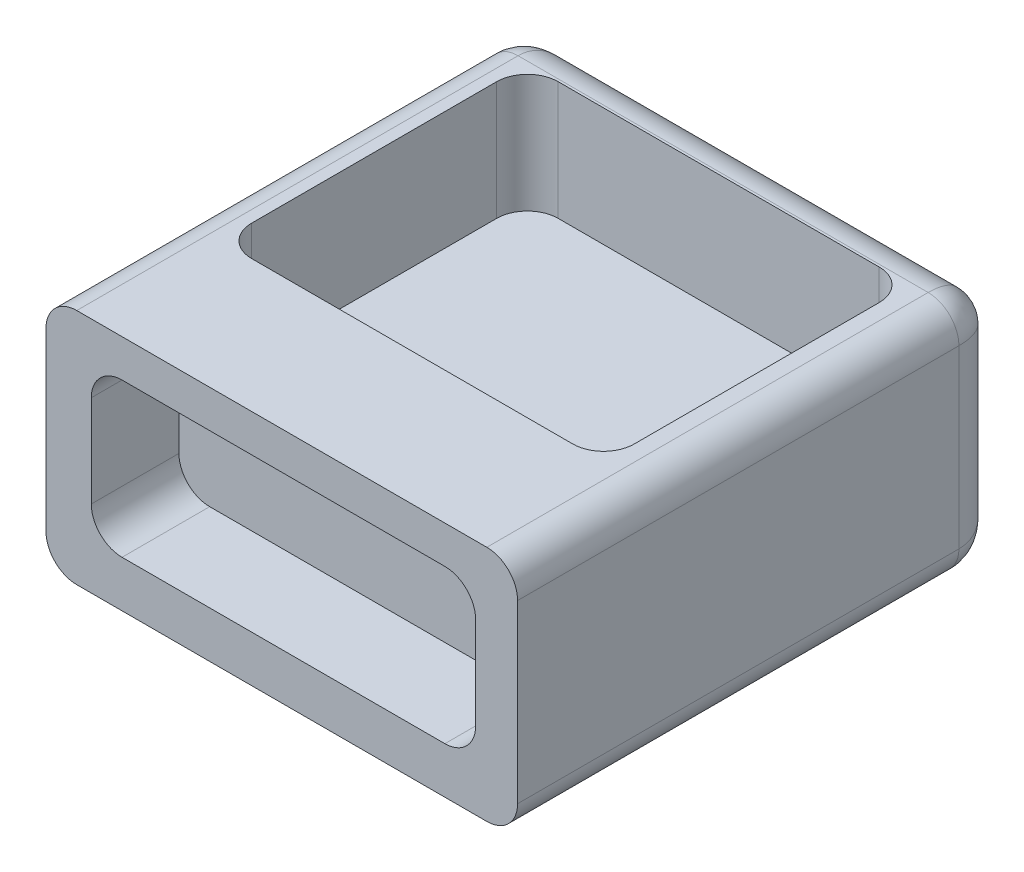
SolidWorks part; units mm, degrees
ref_plane "Front Plane" through (0, 0, 0) normal (0, 0, 1) x (1, 0, 0)
ref_plane "Top Plane" through (0, 0, 0) normal (0, 1, 0) x (1, 0, 0)
ref_plane "Right Plane" through (0, 0, 0) normal (1, 0, 0) x (0, 0, -1)
sketch "Sketch1" plane through (0, 0, 0) normal (0, 0, 1) x (1, 0, 0)
  line L1 (-72.8197, 29.5545) -> (-5.08, 29.5545)
  line L2 (-77.8997, 24.4745) -> (-77.8997, -4.5891)
  line L3 (-72.8197, -9.6691) -> (-5.08, -9.6691)
  line L4 (0, 24.4745) -> (0, -4.5891)
  line L7 (-65.3399, 23.3517) -> (-12.0125, 23.3517)
  line L8 (-70.4199, 18.2717) -> (-70.4199, 3.0732)
  line L9 (-65.3399, -2.0068) -> (-12.0125, -2.0068)
  line L10 (-6.9325, 18.2717) -> (-6.9325, 3.0732)
  arc A0 (-77.8997, -4.5891) -> (-72.8197, -9.6691) centre (-72.8197, -4.5891) ccw
  arc A1 (-5.08, -9.6691) -> (0, -4.5891) centre (-5.08, -4.5891) ccw
  arc A2 (-5.08, 29.5545) -> (0, 24.4745) centre (-5.08, 24.4745) cw
  arc A3 (-72.8197, 29.5545) -> (-77.8997, 24.4745) centre (-72.8197, 24.4745) ccw
  arc A4 (-70.4199, 3.0732) -> (-65.3399, -2.0068) centre (-65.3399, 3.0732) ccw
  arc A5 (-12.0125, -2.0068) -> (-6.9325, 3.0732) centre (-12.0125, 3.0732) ccw
  arc A6 (-12.0125, 23.3517) -> (-6.9325, 18.2717) centre (-12.0125, 18.2717) cw
  arc A7 (-70.4199, 18.2717) -> (-65.3399, 23.3517) centre (-65.3399, 18.2717) cw
  dimension "D1" = 5.08
  dimension "D2" = 5.08
extrude "Boss-Extrude1" add sketch "Sketch1" along normal blind 14.478
sketch "Sketch2" plane through (0, 0, 0) normal (0, 0, -1) x (-1, 0, 0)
  line L1 (5.08, 29.5545) -> (72.8197, 29.5545)
  line L2 (0, 24.4745) -> (0, -4.5891)
  line L3 (5.08, -9.6691) -> (72.8197, -9.6691)
  line L4 (77.8997, 24.4745) -> (77.8997, -4.5891)
  arc A0 (0, -4.5891) -> (5.08, -9.6691) centre (5.08, -4.5891) ccw
  arc A1 (72.8197, -9.6691) -> (77.8997, -4.5891) centre (72.8197, -4.5891) ccw
  arc A2 (72.8197, 29.5545) -> (77.8997, 24.4745) centre (72.8197, 24.4745) cw
  arc A3 (5.08, 29.5545) -> (0, 24.4745) centre (5.08, 24.4745) ccw
  dimension "D1" = 5.08
extrude "Boss-Extrude2" add sketch "Sketch2" along normal blind 66.04
sketch "Sketch3" plane through (-77.8997, 0, 0) normal (-1, 0, 0) x (0, 0, 1)
  line L0 (14.478, 24.4745) -> (14.478, -4.5891) construction
  line L1 (-66.04, 24.4745) -> (14.478, 24.4745)
  line L2 (-66.04, 24.4745) -> (-66.04, 22.9974)
  line L3 (-66.04, 22.9974) -> (14.478, 22.9974)
  line L4 (14.478, 24.4745) -> (14.478, 22.9974)
extrude "Boss-Extrude3" add sketch "Sketch3" against normal blind 1.524
sketch "Sketch4" plane through (-77.8997, 0, 0) normal (-1, 0, 0) x (0, 0, 1)
  line L0 (14.478, 24.4745) -> (14.478, -4.5891) construction
  line L1 (-66.04, 24.4745) -> (14.478, 24.4745)
  line L2 (-66.04, 24.4745) -> (-66.04, 22.9148)
  line L3 (-66.04, 22.9148) -> (14.478, 22.9148)
  line L4 (14.478, 24.4745) -> (14.478, 22.9148)
sketch "Sketch10" plane through (0, 29.5545, 6.7927) normal (0, 1, 0) x (1, 0, 0)
  line L1 (-65.7955, 64.8121) -> (-12.762, 64.8121)
  line L2 (-70.8755, 59.7321) -> (-70.8755, 19.2681)
  line L3 (-65.7955, 14.1881) -> (-12.762, 14.1881)
  line L4 (-7.682, 59.7321) -> (-7.682, 19.2681)
  arc A0 (-70.8755, 19.2681) -> (-65.7955, 14.1881) centre (-65.7955, 19.2681) ccw
  arc A1 (-12.762, 14.1881) -> (-7.682, 19.2681) centre (-12.762, 19.2681) ccw
  arc A2 (-12.762, 64.8121) -> (-7.682, 59.7321) centre (-12.762, 59.7321) cw
  arc A3 (-65.7955, 64.8121) -> (-70.8755, 59.7321) centre (-65.7955, 59.7321) ccw
  dimension "D1" = 5.08
fillet "Fillet5" radius 7.62 8 edges at (-1.4879, 28.0666, -66.04) (-38.9499, 29.5545, -66.04) (-76.4118, 28.0666, -66.04) (-76.4118, -8.1812, -66.04) (-38.9499, -9.6691, -66.04) (-1.4879, -8.1812, -66.04) (-77.8997, 9.9427, -66.04) (0, 9.9427, -66.04)
extrude "Cut-Extrude1" cut sketch "Sketch10" against normal blind 19.558
